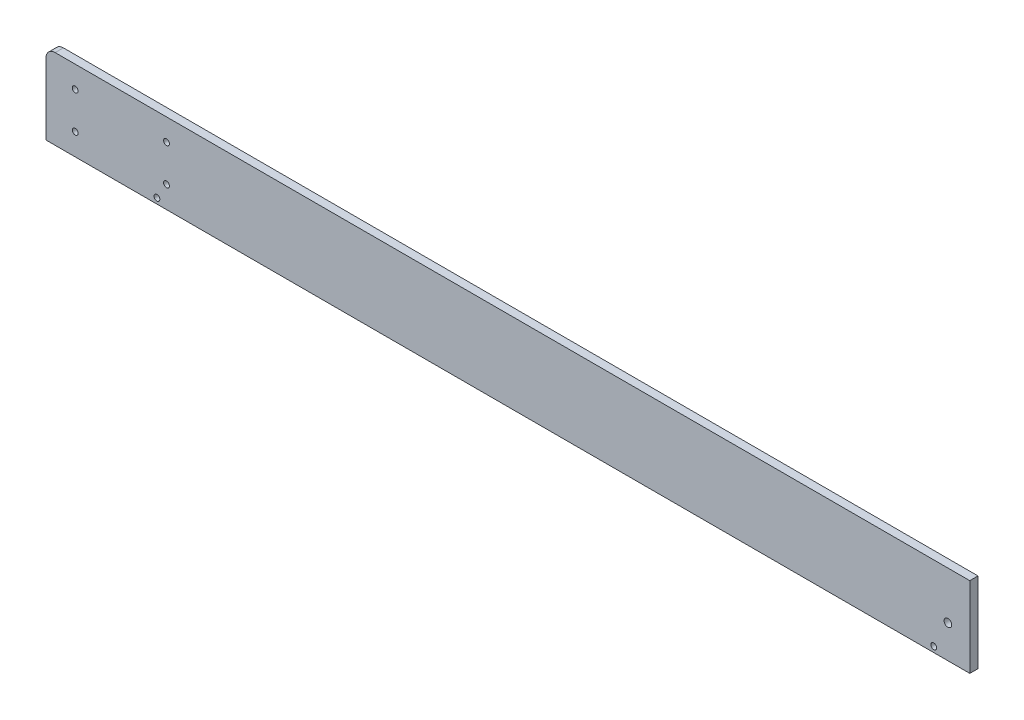
SolidWorks part; units mm, degrees
ref_plane "Front Plane" through (0, 0, 0) normal (0, 0, 1) x (1, 0, 0)
ref_plane "Top Plane" through (0, 0, 0) normal (0, 1, 0) x (1, 0, 0)
ref_plane "Right Plane" through (0, 0, 0) normal (1, 0, 0) x (0, 0, -1)
sketch "Sketch1" plane through (0, 0, 0) normal (0, 0, 1) x (1, 0, 0)
  line L0 (-253, 0) -> (-154.8681, 0) construction
  line L1 (-253, -22) -> (253, -22)
  line L2 (-253, -22) -> (-253, 22)
  line L3 (-253, 22) -> (253, 22)
  line L4 (253, -22) -> (253, 22)
  line L5 (-253, -22) -> (253, 22) construction
  line L6 (-253, 22) -> (253, -22) construction
  line L7 (-247, 6.6679) -> (-247, 39) construction
  circle A0 centre (241, -4) radius 2.1 construction
  circle A1 centre (241, -4) radius 2.1
  circle A2 centre (-237, 10) radius 1.6
  circle A3 centre (-187, 10) radius 1.6
  circle A6 centre (-187, -10) radius 1.6
  circle A9 centre (-237, -10) radius 1.6
  circle A10 centre (233.25, -19) radius 1.6 construction
  circle A11 centre (233.25, -19) radius 1.6
  circle A12 centre (-192.25, -19) radius 1.6 construction
  circle A13 centre (-192.25, -19) radius 1.6
  point P0 (0, 0)
  dimension "D3" = 3.2
  dimension "D1" = 506
  dimension "D2" = 44
  dimension "D4" = 10
  dimension "D5" = 10
  dimension "D6" = 2
  dimension "D7" = 2
extrude "Boss-Extrude1" add sketch "Sketch1" along normal blind 4.5
fillet "Fillet1" radius 5 1 edges at (-253, 22, 2.25)
